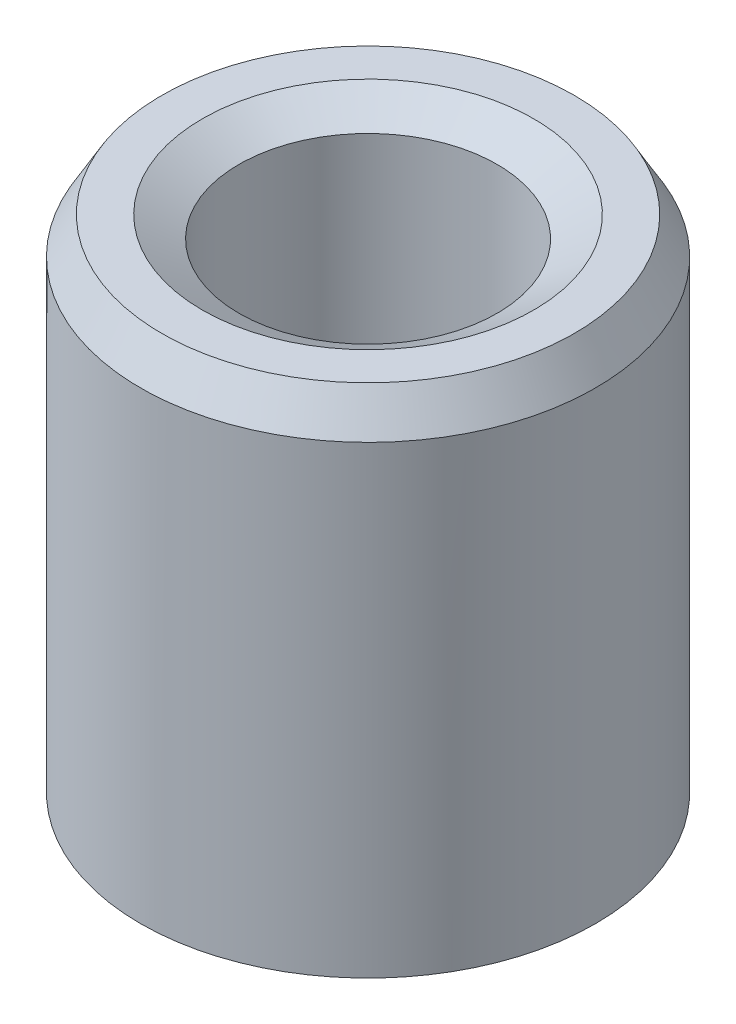
SolidWorks part; units mm, degrees
ref_plane "Front Plane" through (0, 0, 0) normal (0, 0, 1) x (1, 0, 0)
ref_plane "Top Plane" through (0, 0, 0) normal (0, 1, 0) x (1, 0, 0)
ref_plane "Right Plane" through (0, 0, 0) normal (1, 0, 0) x (0, 0, -1)
sketch "Sketch1" plane through (0, 0, 0) normal (0, 1, 0) x (1, 0, 0)
  circle A0 centre (0, 0) radius 17.5
  dimension "SLEEVE_OD" = 35
extrude "Boss-Extrude1" add sketch "Sketch1" along normal blind 40.1491
sketch "Sketch2" plane through (0, 0, 0) normal (0, 1, 0) x (1, 0, 0)
  circle A0 centre (0, 0) radius 9.9317
  dimension "BORE_D" = 19.8634
extrude "Cut-Extrude1" cut sketch "Sketch2" along normal through all
chamfer "Chamfer1" distance 2.8198 angle 30 4 edges at (0, 40.1491, 9.9317) (0, 0, 9.9317) (0, 0, 17.5) (0, 40.1491, 17.5) first distance on face at (0, 40.1491, 9.9317) first distance on face at (0, 0, 9.9317) first distance on face at (0, 40.1491, 17.5)
